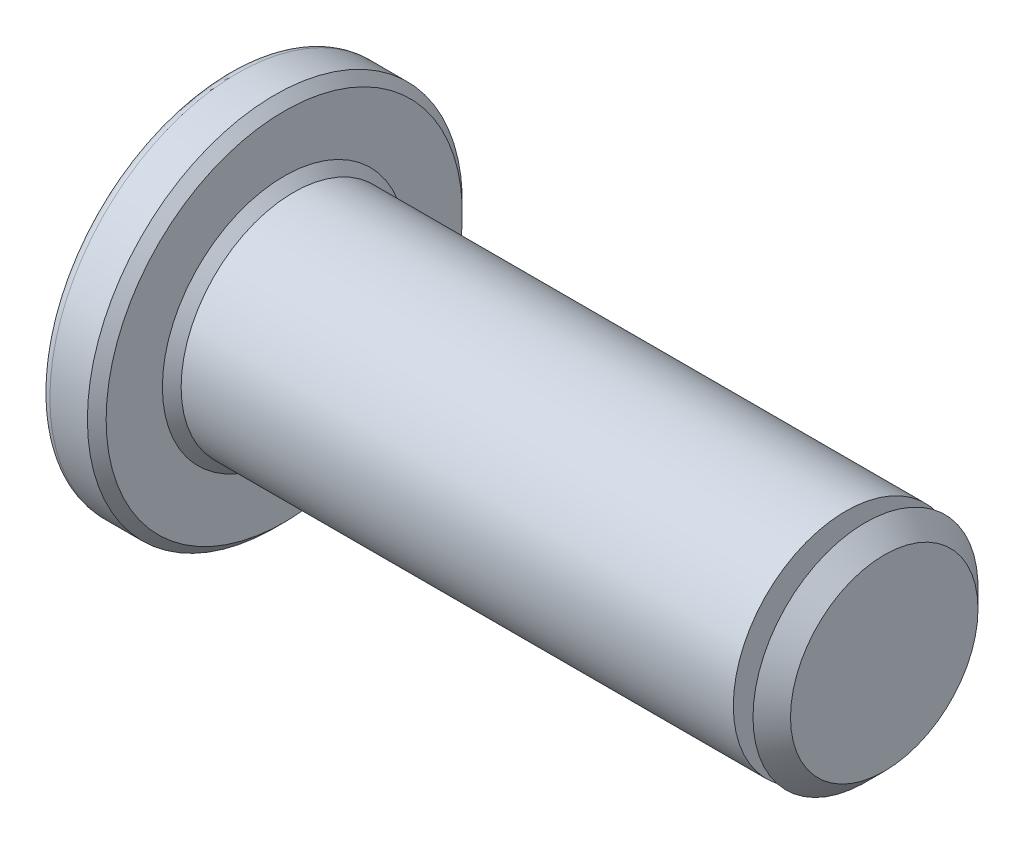
SolidWorks part; units mm, degrees
ref_plane "Piano frontale" through (0, 0, 0) normal (0, 0, 1) x (1, 0, 0)
ref_plane "Piano superiore" through (0, 0, 0) normal (0, 1, 0) x (1, 0, 0)
ref_plane "Piano destro" through (0, 0, 0) normal (1, 0, 0) x (0, 0, -1)
sketch "Schizzo1" plane through (0, 0, 0) normal (0, 0, 1) x (1, 0, 0)
  line L0 (-16.3261, 0) -> (37.1599, 0) construction
  line L1 (0, 0) -> (0, 10)
  line L2 (0, 10) -> (3, 10)
  line L3 (3, 10) -> (3, 6)
  line L4 (3, 6) -> (32.95, 6)
  line L5 (32.95, 6) -> (32.95, 4)
  line L6 (32.95, 4) -> (34, 4)
  line L7 (34, 4) -> (34, 6)
  line L8 (34, 6) -> (35, 6)
  line L9 (35, 6) -> (35, 0)
  line L10 (35, 0) -> (0, 0)
  point P5 (0, 0)
  point P14 (28.4576, 0)
  point P15 (37.1599, 0)
  point P16 (20.6714, 5.5725)
  point P17 (21.2706, 4)
  point P18 (23.0775, 4)
  point P19 (-7.3051, 0)
  point P20 (3.838, 0)
  point P21 (0, 0)
  dimension "D1" = 20
  dimension "D2" = 3
  dimension "D3" = 31
  dimension "D4" = 12
  dimension "D5" = 1.05
  dimension "D6" = 2
  dimension "D7" = 35
revolve "Rivoluzione1" add sketch "Schizzo1" angle 360 about L0
chamfer "Smusso1" distance 0.5 angle 45 1 edges at (3, 0, 10)
chamfer "Smusso2" distance 0.5 angle 45 1 edges at (3, 0, 6)
chamfer "Smusso3" distance 1 angle 45 1 edges at (35, 0, 6)
fillet "Raccordo1" radius 0.5 1 edges at (0, 0, 10)
